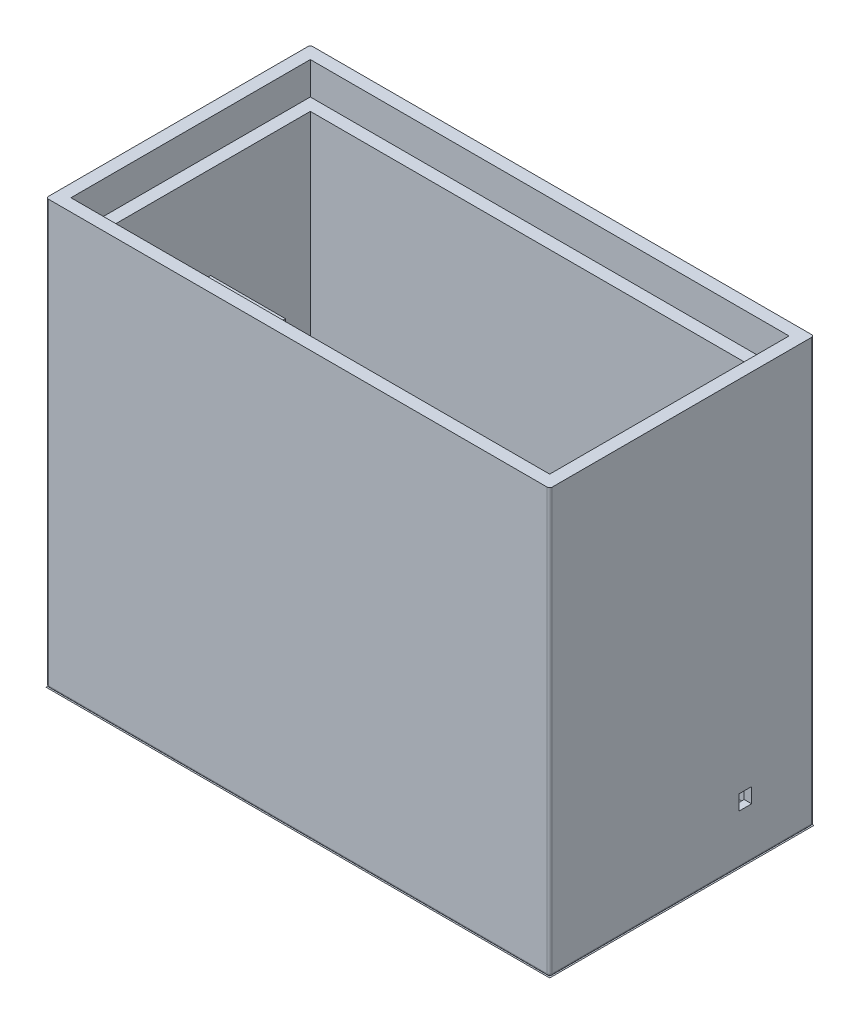
SolidWorks part; units mm, degrees
note: The reader was unsure of these and kept them because the rebuilt part matched: shared geometry of "Sketch1<2>".
ref_plane "Front Plane" through (0, 0, 0) normal (0, 0, 1) x (1, 0, 0)
ref_plane "Top Plane" through (0, 0, 0) normal (0, 1, 0) x (1, 0, 0)
ref_plane "Right Plane" through (0, 0, 0) normal (1, 0, 0) x (0, 0, -1)
sketch "Sketch1" plane through (0, 0, 0) normal (0, 1, 0) x (1, 0, 0)
  line L1 (-9.1, -4.3) -> (9.1, -4.3)
  line L2 (-9.1, -4.3) -> (-9.1, 4.3)
  line L3 (-9.1, 4.3) -> (9.1, 4.3)
  line L4 (9.1, -4.3) -> (9.1, 4.3)
  line L5 (-9.1, -4.3) -> (9.1, 4.3) construction
  line L6 (-9.1, 4.3) -> (9.1, -4.3) construction
  line L7 (-10.1, -5.3) -> (10.1, -5.3)
  line L8 (-10.1, -5.3) -> (-10.1, 5.3)
  line L9 (-10.1, 5.3) -> (10.1, 5.3)
  line L10 (10.1, -5.3) -> (10.1, 5.3)
  line L11 (-10.1, -5.3) -> (10.1, 5.3) construction
  line L12 (-10.1, 5.3) -> (10.1, -5.3) construction
  point P0 (0, 0)
  point P6 (0, 0)
  dimension "D1" = 8.6
  dimension "D2" = 18.2
  dimension "D3" = 10.6
  dimension "D4" = 20.2
surface "Surface-Plane1" sketch "Sketch1"
extrude "Boss-Extrude1" add sketch "Sketch1<2>" along normal blind 17
sketch "Sketch1<2>" plane through (0, 0, 0) normal (0, 1, 0) x (1, 0, 0) same geometry as "Sketch1"
sketch "Sketch3" plane through (-9.1, 0, 0) normal (1, 0, 0) x (0, 0, -1)
  line L0 (0, 0) -> (0, 1)
  line L1 (-4.3, 1) -> (4.3, 1)
  line L2 (4.3, 17) -> (4.3, 0) construction
  line L3 (4.3, 1) -> (4.3, 0)
  line L4 (4.3, 0) -> (-4.3, 0)
  line L5 (-4.3, 1) -> (-4.3, 0)
  point P8 (0, 1)
extrude "Boss-Extrude2" add sketch "Sketch3" along direction (-1, 0, 0) on the side of the normal blind 19.2 contours L5 L4 L3 L1
sketch "Sketch4" plane through (0, 17, 0) normal (0, 1, 0) x (1, 0, 0)
  line L3 (-9.6, -4.8) -> (9.6, -4.8)
  line L4 (-9.6, -4.8) -> (-9.6, 4.8)
  line L5 (-9.6, 4.8) -> (9.6, 4.8)
  line L6 (9.6, -4.8) -> (9.6, 4.8)
  dimension "D1" = 9.6
extrude "Cut-Extrude1" cut sketch "Sketch4" against normal blind 1.3
sketch "Sketch6" plane through (0, 0, 0) normal (0, -1, 0) x (1, 0, 0)
  line L1 (-10.1, 5.3) -> (10.1, 5.3) construction
  circle A0 centre (0, 2) radius 1.5
  dimension "D1" = 3
  dimension "D2" = 3.3
extrude "Cut-Extrude2" cut sketch "Sketch6" against normal up to next
sketch "Sketch8" plane through (-9.1, 0, 0) normal (1, 0, 0) x (0, 0, -1)
  line L2 (0.3, 1) -> (0.3, 12)
  line L3 (-4.3, 1) -> (4.3, 1) construction
  line L4 (0.3, 12) -> (-0.1, 12)
  line L5 (-0.1, 12) -> (-0.1, 1)
  line L6 (-0.1, 1) -> (0.3, 1)
  dimension "D2" = 0.4
  dimension "D3" = 11
extrude "Boss-Extrude3" add sketch "Sketch8" along normal blind 3
ref_plane "Plane1" through (0, 0, 0) normal (1, 0, 0) x (0, 0, -1)
mirror "Mirror1" about plane through (0, 0, 0) normal (1, 0, 0) of "Boss-Extrude3"
sketch "Sketch11" plane through (-9.1, 0, 0) normal (1, 0, 0) x (0, 0, -1)
  line L0 (0.3, 1) -> (0.3, 12) construction
  line L1 (2.3, 2) -> (2.8, 2)
  line L2 (2.3, 2) -> (2.3, 2.6)
  line L3 (2.3, 2.6) -> (2.8, 2.6)
  line L4 (2.8, 2) -> (2.8, 2.6)
  line L5 (0.3, 1) -> (4.3, 1) construction
  dimension "D1" = 2
  dimension "D2" = 1
  dimension "D3" = 0.6
  dimension "D4" = 0.5
extrude "Cut-Extrude3" cut sketch "Sketch11" against normal through all both and the other way through all
fillet "Fillet12" radius 0.1 4 edges at (-10.1, 8.5, -5.3) (-10.1, 8.5, 5.3) (10.1, 8.5, 5.3) (10.1, 8.5, -5.3)
fillet "Fillet13" radius 0.1 8 edges at (-10.0707, 0, -5.2707) (0, 0, -5.3) (10.0707, 0, -5.2707) (10.1, 0, 0) (10.0707, 0, 5.2707) (0, 0, 5.3) (-10.0707, 0, 5.2707) (-10.1, 0, 0)
sketch "Sketch13" plane through (-9.1, 0, 0) normal (1, 0, 0) x (0, 0, -1)
  line L0 (2.8, 2.6) -> (2.3, 2.6) construction
  line L1 (1.5, 3.1) -> (3.2, 3.1)
  line L2 (1.5, 3.1) -> (1.5, 1.5)
  line L3 (1.5, 1.5) -> (3.2, 1.5)
  line L4 (3.2, 3.1) -> (3.2, 1.5)
  line L5 (2.3, 2) -> (2.8, 2) construction
  line L6 (2.8, 2) -> (2.8, 2.6) construction
  line L7 (2.3, 2.6) -> (2.3, 2) construction
  dimension "D1" = 0.5
  dimension "D2" = 0.5
  dimension "D3" = 0.4
  dimension "D4" = 0.8
extrude "Cut-Extrude4" cut sketch "Sketch13" against normal blind 0.7
mirror "Mirror2" about plane through (0, 0, 0) normal (1, 0, 0) of "Cut-Extrude4"
